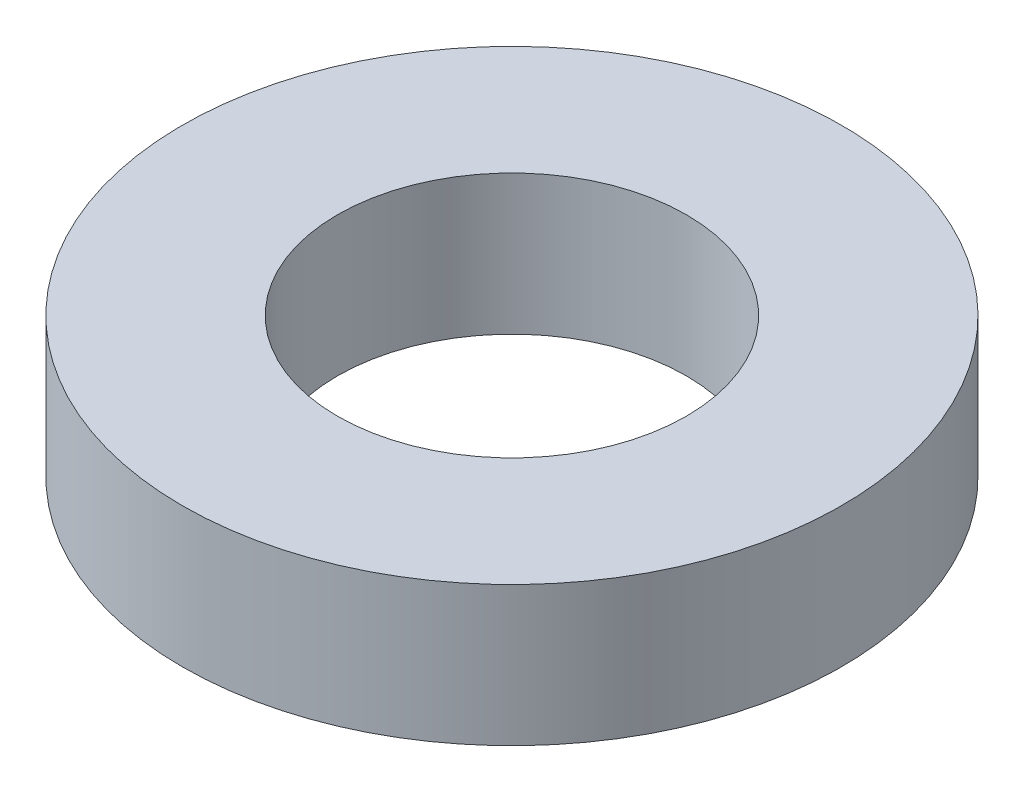
SolidWorks part; units mm, degrees
ref_plane "Front Plane" through (0, 0, 0) normal (0, 0, 1) x (1, 0, 0)
ref_plane "Top Plane" through (0, 0, 0) normal (0, 1, 0) x (1, 0, 0)
ref_plane "Right Plane" through (0, 0, 0) normal (1, 0, 0) x (0, 0, -1)
sketch "Sketch1" plane through (0, 0, 0) normal (0, 1, 0) x (1, 0, 0)
  circle A0 centre (0, 0) radius 42.5
  dimension "FLANGE_OD" = 85
extrude "Boss-Extrude1" add sketch "Sketch1" along normal blind 18
sketch "Sketch2" plane through (0, 0, 0) normal (0, 1, 0) x (1, 0, 0)
  circle A0 centre (0, 0) radius 22.5
  dimension "BORE_D" = 45
extrude "Cut-Extrude1" cut sketch "Sketch2" along normal through all
sketch "Sketch3" plane through (0, 18, 0) normal (0, 1, 0) x (1, 0, 0)
  circle A0 centre (0, 0) radius 13.5816 construction
  circle A1 centre (-13.5816, 0) radius 2.2721
  dimension "BOLT_D" = 4.5441
  dimension "BOLT_PCD" = 27.1631
extrude "Cut-Extrude2" cut sketch "Sketch3" against normal blind 17.7273 rebuild error yes
pattern_circular "CirPattern1" count 3 over 360 rebuild error yes
